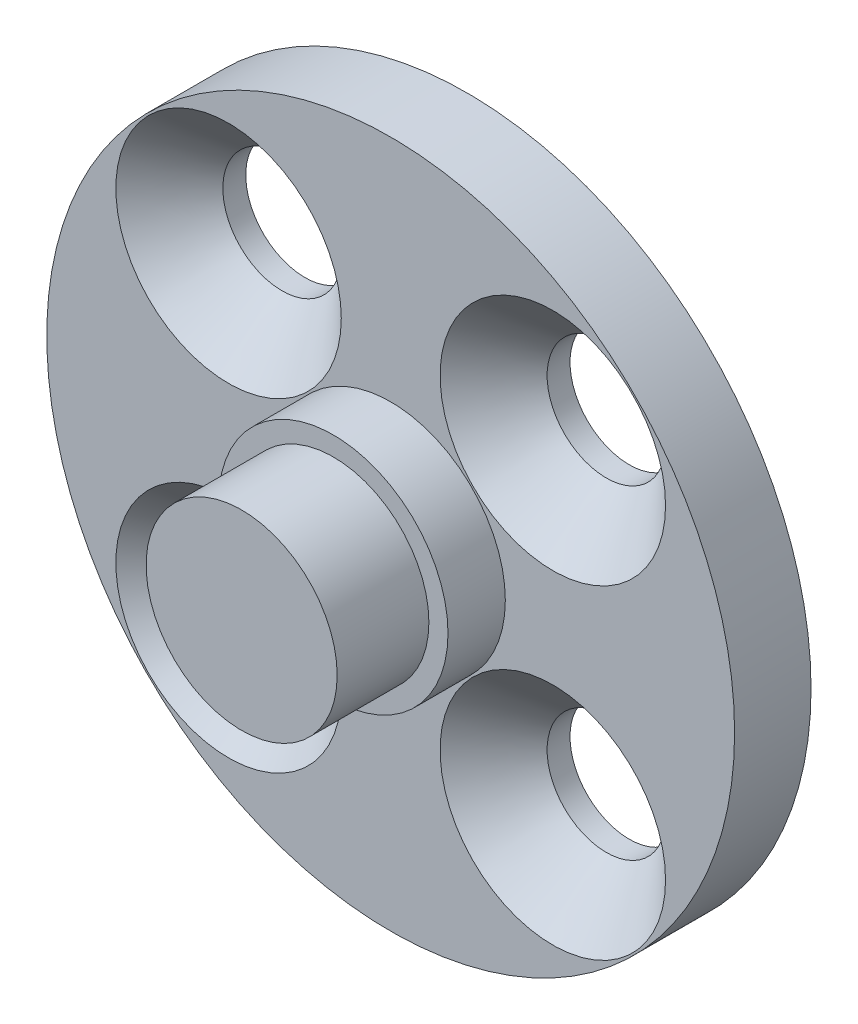
SolidWorks part; units mm, degrees
ref_plane "Front Plane" through (0, 0, 0) normal (1, 0, 0) x (0, 1, 0)
ref_plane "Top Plane" through (0, 0, 0) normal (0, 0, 1) x (0, 1, 0)
ref_plane "Right Plane" through (0, 0, 0) normal (0, 1, 0) x (-1, 0, 0)
ref_axis "x axis" through (-88.99, 0, 0) along (1, 0, 0)
ref_axis "y xxis" through (0, 88.99, 0) along (0, -1, 0)
ref_axis "z axis" through (0, 0, 55) along (0, 0, -1)
sketch "Sketch1" plane through (0, 0, 0) normal (0, 0, 1) x (0, 1, 0)
  line L1 (-4.2426, -4.2426) -> (4.2426, -4.2426) construction
  line L2 (-4.2426, -4.2426) -> (-4.2426, 4.2426) construction
  line L3 (-4.2426, 4.2426) -> (4.2426, 4.2426) construction
  line L4 (4.2426, -4.2426) -> (4.2426, 4.2426) construction
  line L5 (-4.2426, -4.2426) -> (4.2426, 4.2426) construction
  line L6 (-4.2426, 4.2426) -> (4.2426, -4.2426) construction
  circle A3 centre (0, 0) radius 9
  circle A4 centre (-4.2426, 4.2426) radius 1.55
  circle A5 centre (4.2426, 4.2426) radius 1.55
  circle A6 centre (4.2426, -4.2426) radius 1.55
  circle A7 centre (-4.2426, -4.2426) radius 1.55
  dimension "D1" = 18
  dimension "D2" = 12
  dimension "D3" = 3.1
extrude "Boss-Extrude1" add sketch "Sketch1" along normal blind 2
sketch "Sketch2" plane through (0, 0, 2) normal (0, 0, 1) x (1, 0, 0)
  circle A0 centre (0, 0) radius 3
  dimension "D1" = 6
extrude "Boss-Extrude2" add sketch "Sketch2" along normal blind 1.5
sketch "Sketch3" plane through (0, 0, 3.5) normal (0, 0, 1) x (1, 0, 0)
  circle A0 centre (0, 0) radius 2.5
  dimension "D1" = 5
extrude "Boss-Extrude3" add sketch "Sketch3" along normal blind 2.4
chamfer "Chamfer1" distance 1.4 angle 45 4 edges at (-2.6926, 4.2426, 2) (-2.6926, -4.2426, 2) (5.7926, -4.2426, 2) (5.7926, 4.2426, 2)
